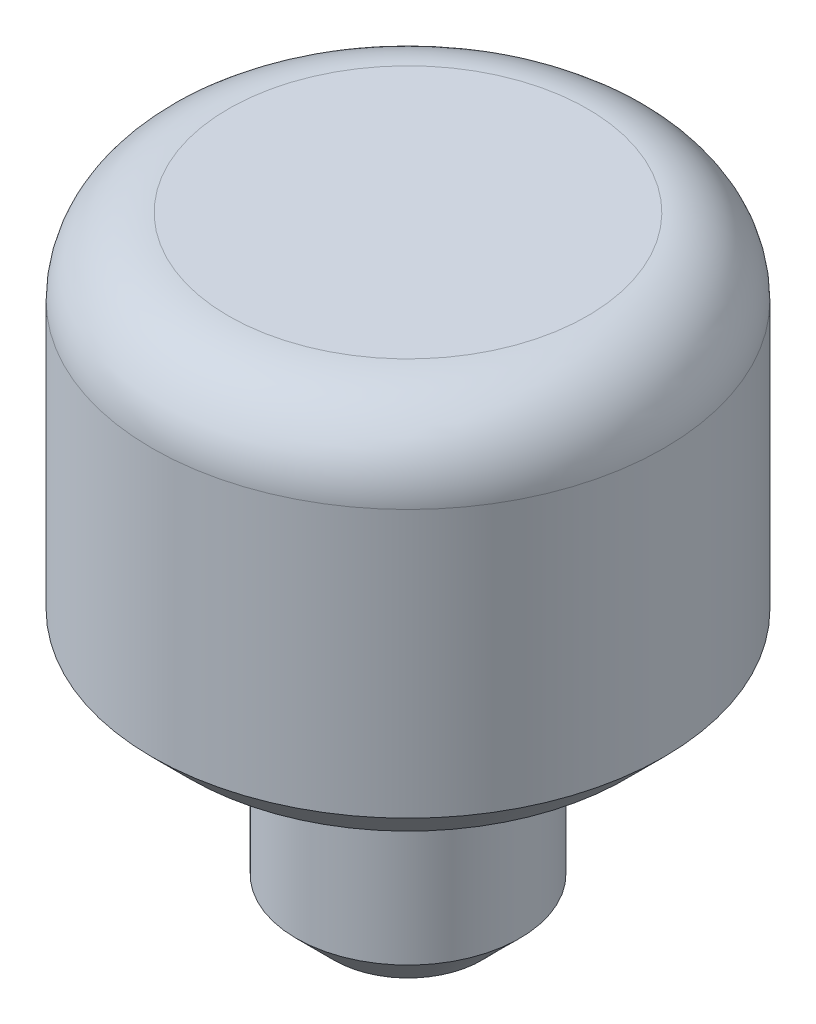
SolidWorks part; units mm, degrees
material "ABS"
ref_plane "Front" through (0, 0, 0) normal (0, 0, 1) x (1, 0, 0)
ref_plane "Top" through (0, 0, 0) normal (0, 1, 0) x (1, 0, 0)
ref_plane "Right" through (0, 0, 0) normal (1, 0, 0) x (0, 0, -1)
sketch "Эскиз1" plane through (0, 0, 0) normal (0, 1, 0) x (1, 0, 0)
  circle A7 centre (0, 0) radius 6.7
  circle A8 centre (0, 0) radius 2.925
  dimension "D1" = 13.4
  dimension "D2" = 5.85
extrude "Бобышка-Вытянуть1" add sketch "Эскиз1" along normal blind 10 contours A7
extrude "Бобышка-Вытянуть2" add sketch "Эскиз1<5>" against normal blind 6 contours A8
sketch "Эскиз1<5>" plane through (0, 0, 0) normal (0, 1, 0) x (1, 0, 0) same geometry as "Эскиз1"
chamfer "Фаска1" distance 1 angle 45 2 edges at (0, -6, 2.925) (0, 0, 6.7)
fillet "Скругление1" radius 0.4 1 edges at (0, 0, 2.925)
fillet "Скругление2" radius 2 1 edges at (0, 10, 6.7)
